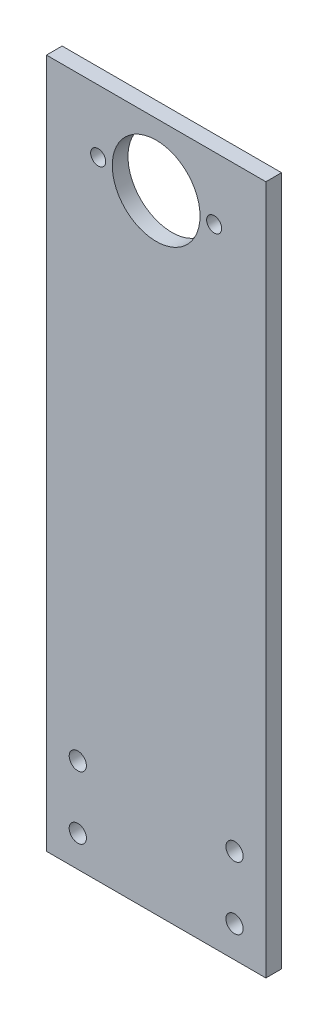
SolidWorks part; units mm, degrees
ref_plane "Front Plane" through (0, 0, 0) normal (0, 0, 1) x (1, 0, 0)
ref_plane "Top Plane" through (0, 0, 0) normal (0, 1, 0) x (1, 0, 0)
ref_plane "Right Plane" through (0, 0, 0) normal (1, 0, 0) x (0, 0, -1)
sketch "Sketch1" plane through (0, 0, 0) normal (0, 0, 1) x (1, 0, 0)
  line L0 (0, 0) -> (0, 100) construction
  line L1 (-35, -100) -> (35, -100) construction
  line L2 (-35, -100) -> (-35, 100)
  line L3 (-35, 100) -> (35, 100)
  line L4 (35, -100) -> (35, 100)
  line L5 (-35, -100) -> (35, 100) construction
  line L6 (-35, 100) -> (35, -100) construction
  line L7 (-18.5, 80) -> (18.5, 80) construction
  line L8 (0, 0) -> (0, -100) construction
  line L9 (-25, -90) -> (25, -90) construction
  line L10 (-35, -100) -> (-35, -120)
  line L11 (56.5225, -120) -> (-643.4775, -120) construction
  line L12 (-35, -120) -> (35, -120)
  line L13 (35, -120) -> (35, -100)
  circle A0 centre (-18.5, 80) radius 2.4
  circle A1 centre (18.5, 80) radius 2.4
  circle A2 centre (0, 80) radius 5
  circle A3 centre (-25, -90) radius 2.75
  circle A4 centre (25, -90) radius 2.75
  circle A5 centre (25, -110) radius 2.75
  circle A6 centre (-25, -110) radius 2.75
  circle A7 centre (0, 80) radius 14
  point P0 (0, 0)
  point P10 (0, 80)
  point P18 (0, -90)
  dimension "D4" = 4.8
  dimension "D5" = 10
  dimension "D6" = 5.5
  dimension "D11" = 28
  dimension "D1" = 70
  dimension "D2" = 200
  dimension "D3" = 37
  dimension "D7" = 10
  dimension "D8" = 20
  dimension "D9" = 10
  dimension "D10" = 20
extrude "Boss-Extrude1" add sketch "Sketch1" along normal blind 5 contours L12 L13 L4 L3 L2 L10 A7 A6 A5 A4 A3 A1 A0 region at (0, -13.4206, 0)
